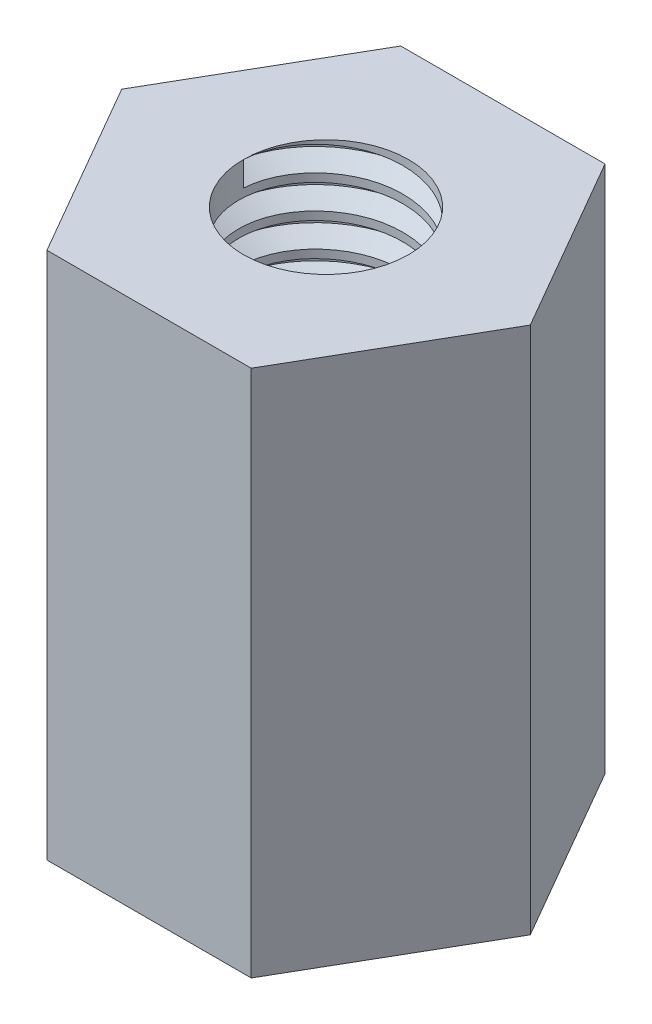
SolidWorks part; units mm, degrees
ref_plane "Front Plane" through (0, 0, 0) normal (0, 0, 1) x (1, 0, 0)
ref_plane "Top Plane" through (0, 0, 0) normal (0, 1, 0) x (1, 0, 0)
ref_plane "Right Plane" through (0, 0, 0) normal (1, 0, 0) x (0, 0, -1)
sketch "Sketch1" plane through (0, 0, 0) normal (0, 1, 0) x (1, 0, 0)
  line L1 (3.0946, 0) -> (1.5473, 2.68)
  line L2 (1.5473, 2.68) -> (-1.5473, 2.68)
  line L3 (-1.5473, 2.68) -> (-3.0946, 0)
  line L4 (-3.0946, 0) -> (-1.5473, -2.68)
  line L5 (-1.5473, -2.68) -> (1.5473, -2.68)
  line L6 (1.5473, -2.68) -> (3.0946, 0)
  circle A0 centre (0, 0) radius 2.68 construction
  circle A1 centre (0, 0) radius 1.25
extrude "Boss-Extrude1" add sketch "Sketch1" along normal blind 8
thread "Thread1" pitch 0.5 method cut profile "Thread Profile1" start angle 0, offset 0, length 8, pitch 0.5, diameter 2.5
ref_plane "Plane1" through (-1.25, 8, 0) normal (0, 0, 1) x (-1, 0, 0)
sketch "Thread Profile1" plane through (-1.25, 8, 0) normal (0, 0, 1) x (-1, 0, 0)
  line L0 (0, 0) -> (0, 0.5) construction
  line L1 (0, 0) -> (0.2706, 0.1562)
  line L2 (0.2706, 0.1562) -> (0.2706, 0.2187)
  line L3 (0.2706, 0.2187) -> (0, 0.375)
  line L4 (0.2706, 0.1875) -> (0, 0.1875) construction
  line L11 (0, 0) -> (0, 0.375)
  point P2 (0, 0)
  dimension "Pitch" = 0.5
  dimension "Profile_Angle" = 60
  dimension "Profile_Land" = 0.0625
  dimension "Profile_Height" = 0.2706
